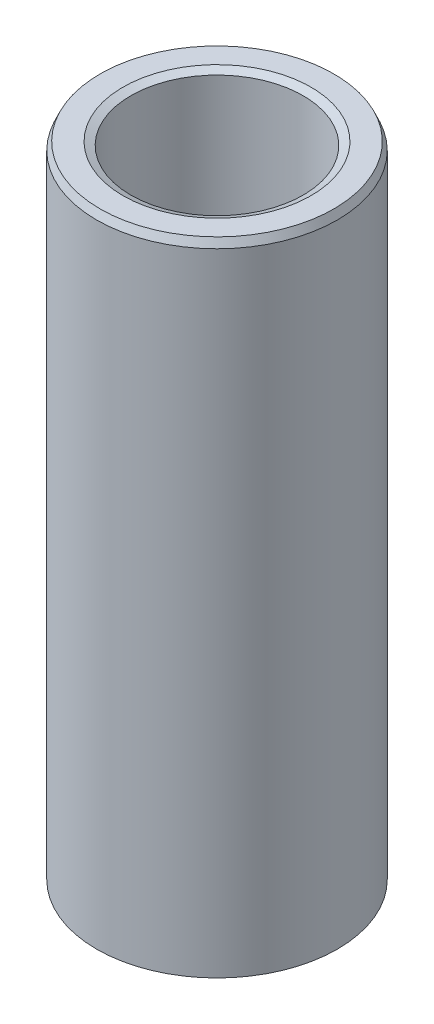
SolidWorks part; units mm, degrees
ref_plane "Front Plane" through (0, 0, 0) normal (0, 0, 1) x (1, 0, 0)
ref_plane "Top Plane" through (0, 0, 0) normal (0, 1, 0) x (1, 0, 0)
ref_plane "Right Plane" through (0, 0, 0) normal (1, 0, 0) x (0, 0, -1)
sketch "Sketch1" plane through (0, 0, 0) normal (0, 1, 0) x (1, 0, 0)
  circle A0 centre (0, 0) radius 55
  dimension "SLEEVE_OD" = 110
extrude "Boss-Extrude1" add sketch "Sketch1" along normal blind 293.6918
sketch "Sketch2" plane through (0, 0, 0) normal (0, 1, 0) x (1, 0, 0)
  circle A0 centre (0, 0) radius 39.3657
  dimension "BORE_D" = 78.7314
extrude "Cut-Extrude1" cut sketch "Sketch2" along normal through all
chamfer "Chamfer1" distance 3.5967 angle 23.725 4 edges at (0, 293.6918, 39.3657) (0, 0, 39.3657) (0, 0, 55) (0, 293.6918, 55) first distance on face at (0, 293.6918, 39.3657) first distance on face at (0, 0, 39.3657) first distance on face at (0, 293.6918, 55)
